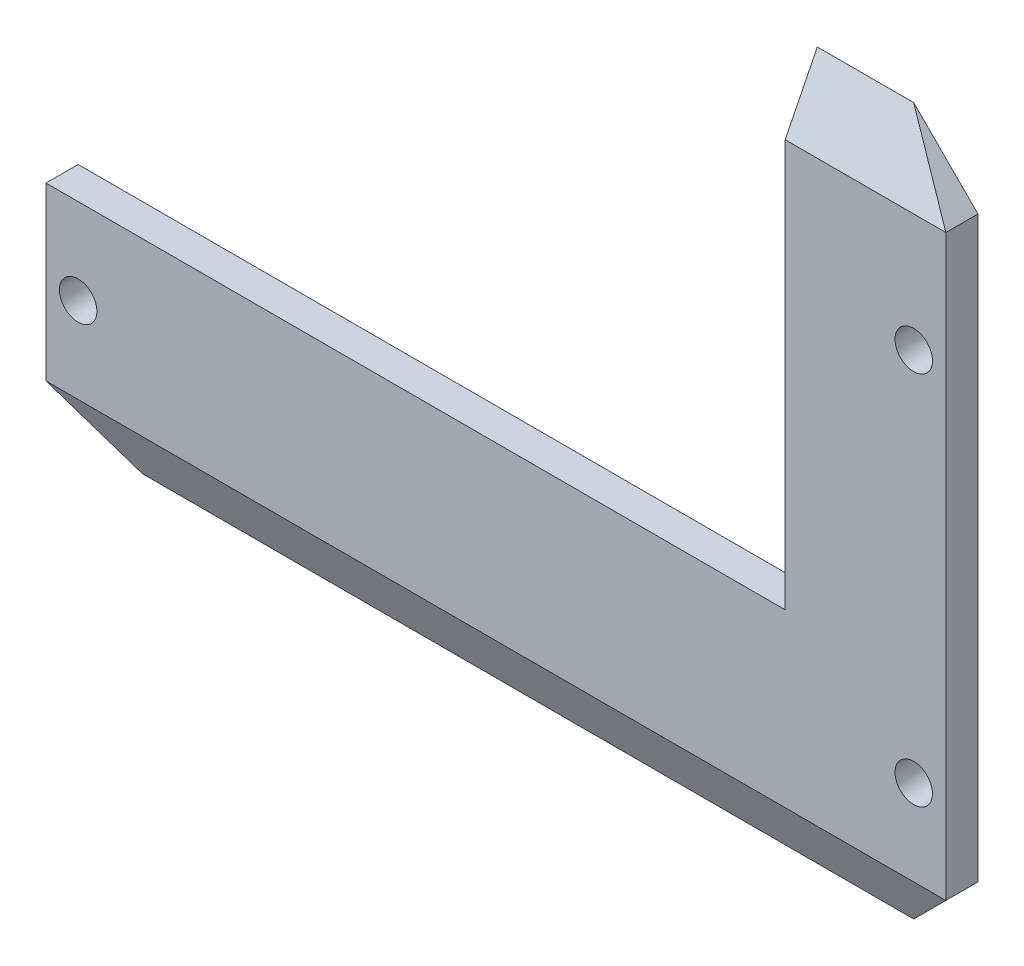
SolidWorks part; units mm, degrees
ref_plane "Front Plane" through (0, 0, 0) normal (0, 0, 1) x (1, 0, 0)
ref_plane "Top Plane" through (0, 0, 0) normal (0, 1, 0) x (1, 0, 0)
ref_plane "Right Plane" through (0, 0, 0) normal (1, 0, 0) x (0, 0, -1)
sketch "Sketch1" plane through (0, 0, 0) normal (0, 0, 1) x (1, 0, 0)
  line L1 (-42, -33) -> (42, -33)
  line L2 (-42, -33) -> (-42, 33)
  line L3 (-42, 33) -> (42, 33)
  line L4 (42, -33) -> (42, 33)
  line L5 (-42, -33) -> (42, 33) construction
  line L6 (-42, 33) -> (42, -33) construction
  point P0 (0, 0)
  dimension "D1" = 84
  dimension "D2" = 66
extrude "Boss-Extrude1" add sketch "Sketch1" along normal blind 3
chamfer "Chamfer2" distance 6 distance2 6 4 edges at (42, -33, 1.5) (-42, -33, 1.5) (-42, 33, 1.5) (42, 33, 1.5)
chamfer "Chamfer4" distance 3 distance2 6 2 edges at (0, -33, 3) (0, 33, 3)
sketch "Sketch2" plane through (0, 0, 3) normal (0, 0, 1) x (1, 0, 0)
  line L0 (-42, -19) -> (42, -19) construction
  line L1 (-42, 27) -> (-42, -27) construction
  line L2 (-42, 16) -> (42, 16) construction
  line L3 (0, 3) -> (0, 13.7383) construction
  line L4 (-36, -33) -> (36, -33) construction
  line L5 (-42, 27) -> (-42, -27) construction
  line L6 (36, 33) -> (-36, 33) construction
  line L7 (42, -27) -> (42, 27) construction
  circle A0 centre (-39, -19) radius 1.75
  circle A1 centre (39, -19) radius 1.75
  circle A2 centre (39, 16) radius 1.75
  circle A3 centre (-39, 16) radius 1.75
  dimension "D1" = 3.5
  dimension "D7" = 3.5
  dimension "D8" = 3.5
  dimension "D2" = 3
  dimension "D3" = 14
  dimension "D4" = 17
  dimension "D5" = 3
  dimension "D6" = 3
extrude "Cut-Extrude1" cut sketch "Sketch2" against normal through all
sketch "Sketch3" plane through (0, 0, 3) normal (0, 0, 1) x (1, 0, 0)
  line L0 (36, 33) -> (-36, 33) construction
  line L1 (27, -11) -> (-42, -11)
  line L2 (27, -11) -> (27, 33)
  line L3 (27, 33) -> (-42, 33)
  line L4 (-42, -11) -> (-42, 33)
  line L5 (-42, 27) -> (-42, -27) construction
  line L6 (-36, -33) -> (36, -33) construction
  line L7 (42, -27) -> (42, 27) construction
  dimension "D1" = 22
  dimension "D2" = 15
extrude "Cut-Extrude2" cut sketch "Sketch3" against normal blind 10
